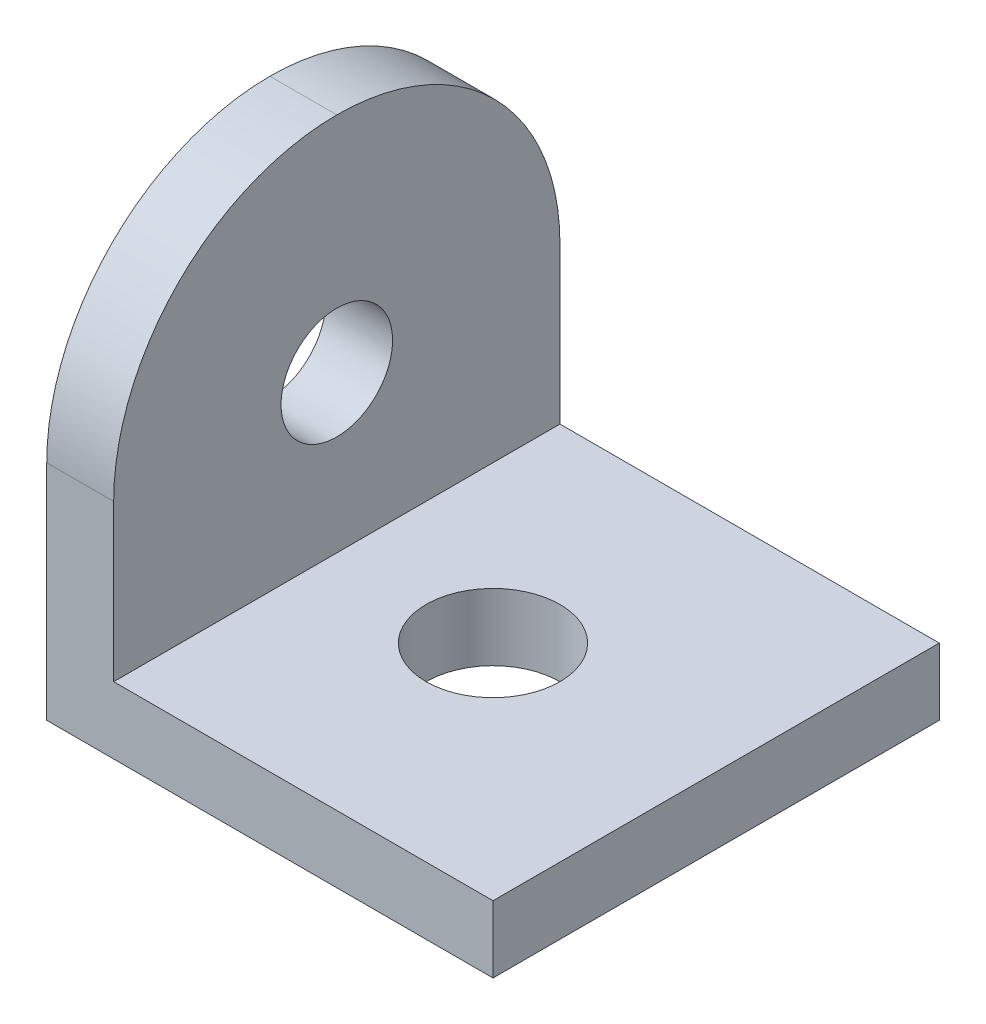
SolidWorks part; units mm, degrees
ref_plane "前视基准面" through (0, 0, 0) normal (0, 0, 1) x (1, 0, 0)
ref_plane "上视基准面" through (0, 0, 0) normal (0, 1, 0) x (1, 0, 0)
ref_plane "右视基准面" through (0, 0, 0) normal (1, 0, 0) x (0, 0, -1)
other "Configuration Table"
sketch "草图1" plane through (0, 0, 0) normal (0, 1, 0) x (1, 0, 0)
  line L1 (-10, 10) -> (10, 10)
  line L2 (-10, 10) -> (-10, -10)
  line L3 (-10, -10) -> (10, -10)
  line L4 (10, 10) -> (10, -10)
  line L5 (-10, 10) -> (10, -10) construction
  line L6 (-10, -10) -> (10, 10) construction
  point P0 (0, 0)
  dimension "D1" = 20
  dimension "D2" = 20
extrude "凸台-拉伸1" add sketch "草图1" along normal blind 20
sketch "草图2" plane through (0, 0, 10) normal (0, 0, 1) x (1, 0, 0)
  line L0 (-7, 20) -> (-7, 3)
  line L1 (-10, 20) -> (10, 20) construction
  line L2 (-7, 3) -> (10, 3)
  line L3 (10, 20) -> (10, 0) construction
  line L4 (10, 3) -> (10, 20)
  line L5 (10, 20) -> (-7, 20)
  line L6 (-10, 0) -> (10, 0) construction
  line L7 (-10, 20) -> (-10, 0) construction
  dimension "D1" = 3
  dimension "D2" = 3
extrude "切除-拉伸1" cut sketch "草图2" against normal blind 20
fillet "圆角1" radius 10 2 edges at (-8.5, 20, -10) (-8.5, 20, 10)
sketch "草图3" plane through (-7, 0, 0) normal (1, 0, 0) x (0, 0, -1)
  circle A0 centre (0, 10) radius 2.5
  dimension "D1" = 5
extrude "切除-拉伸2" cut sketch "草图3" against normal blind 20
sketch "草图4" plane through (0, 3, 0) normal (0, 1, 0) x (1, 0, 0)
  circle A0 centre (0, 0) radius 3
  dimension "D1" = 6
extrude "切除-拉伸3" cut sketch "草图4" against normal blind 20
